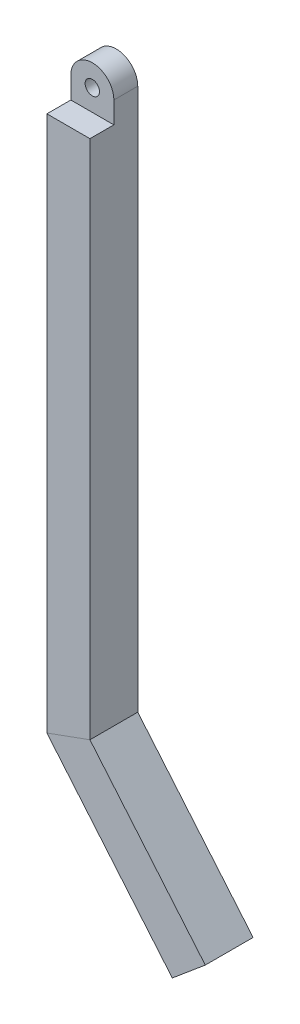
SolidWorks part; units mm, degrees
ref_plane "前视基准面" through (0, 0, 0) normal (0, 0, 1) x (1, 0, 0)
ref_plane "上视基准面" through (0, 0, 0) normal (0, 1, 0) x (1, 0, 0)
ref_plane "右视基准面" through (0, 0, 0) normal (1, 0, 0) x (0, 0, -1)
sketch "草图4" plane through (0, 0, 0) normal (0, 1, 0) x (1, 0, 0)
  line L0 (-24.3, 1.0429) -> (-15.3, 1.0429)
  line L1 (-15.3, 1.0429) -> (-15.3, -8.9571)
  line L2 (-15.3, -8.9571) -> (-24.3, -8.9571)
  line L3 (-24.3, -8.9571) -> (-24.3, 1.0429)
  line L4 (-24.3, 1.0429) -> (-15.3, -8.9571) construction
  line L5 (-15.3, 1.0429) -> (-24.3, -8.9571) construction
  point P3 (-19.8, -3.9571)
  dimension "D1" = 9
  dimension "D2" = 10
extrude "凸台-拉伸2" add sketch "草图4" along normal blind 10
ref_plane "镜腿扫描轨迹基准面" through (0, 0, 3.9571) normal (0, 0, 1) x (1, 0, 0)
sketch "草图5" plane through (0, 0, 3.9571) normal (0, 0, 1) x (1, 0, 0)
  line L0 (-19.8, 0) -> (-19.8, -110)
  line L1 (-24.3, 0) -> (-15.3, 0) construction
  line L2 (-19.8, -110) -> (5.373, -140)
  dimension "D1" = 110
  dimension "D2" = 30
  dimension "D3" = 140
sketch "草图6" plane through (0, 0, 8.9571) normal (0, 0, 1) x (1, 0, 0)
  line L0 (-24.3, 10) -> (-24.3, 5)
  line L1 (-24.3, 10) -> (-24.3, 0) construction
  line L2 (-24.3, 10) -> (-15.3, 10)
  line L3 (-15.3, 10) -> (-15.3, 5)
  line L4 (-15.3, 10) -> (-15.3, 0) construction
  arc A0 (-24.3, 5) -> (-15.3, 5) centre (-19.8, 5) cw
  dimension "D1" = 5
  dimension "D2" = 5
extrude "切除-拉伸1" cut sketch "草图6" against normal blind 10
sweep "扫描2" add profiles "草图4<2>" path "草图5"
sketch "草图4<2>" plane through (0, 0, 0) normal (0, 1, 0) x (1, 0, 0) same geometry as "草图4"
ref_plane "connection口生成草图基准面" through (0, 0, 3.9571) normal (0, 0, 1) x (1, 0, 0)
sketch "草图7" plane through (0, 0, 3.9571) normal (0, 0, 1) x (1, 0, 0)
  line L0 (-24.3, 5) -> (-24.3, 0.5)
  line L1 (-24.3, 5) -> (-24.3, -111.6379) construction
  line L2 (-24.3, 0.5) -> (-15.3, 0.5)
  line L3 (-15.3, 5) -> (-15.3, -108.3621) construction
  line L4 (-15.3, 0.5) -> (-15.3, 5)
  arc A0 (-24.3, 5) -> (-15.3, 5) centre (-19.8, 5) cw
  dimension "D1" = 4.5
extrude "切除-拉伸2" cut sketch "草图7" along normal blind 10
sketch "草图8" plane through (0, 0, 3.9571) normal (0, 0, 1) x (1, 0, 0)
  line L3 (-15.3, 0.5) -> (-15.3, 5)
  line L4 (-24.3, 0.5) -> (-15.3, 0.5)
  line L5 (-24.3, 5) -> (-24.3, 0.5)
  line L6 (-15.3, 0.5) -> (-15.3, 5)
  line L7 (-24.3, 0.5) -> (-15.3, 0.5)
  line L8 (-24.3, 5) -> (-24.3, 0.5)
  circle A0 centre (-19.8, 5) radius 1.5
  arc A1 (-15.3, 5) -> (-24.3, 5) centre (-19.8, 5) ccw
  arc A2 (-15.3, 5) -> (-24.3, 5) centre (-19.8, 5) ccw
  dimension "D2" = 3
  dimension "D1" = 0
extrude "切除-拉伸3" cut sketch "草图8" against normal blind 10 contours A0
